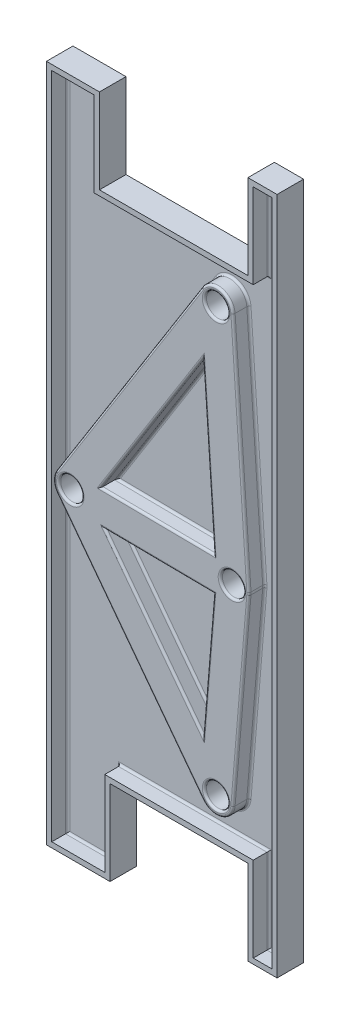
SolidWorks part; units mm, degrees
ref_plane "Plan de face" through (0, 0, 0) normal (0, 0, 1) x (1, 0, 0)
ref_plane "Plan de dessus" through (0, 0, 0) normal (0, 1, 0) x (1, 0, 0)
ref_plane "Plan de droite" through (0, 0, 0) normal (1, 0, 0) x (0, 0, -1)
sketch "Esquisse1" plane through (0, 0, 0) normal (0, 0, 1) x (1, 0, 0)
  line L0 (12, -64) -> (19.5, -64)
  line L1 (-12, -64) -> (12, -64)
  line L2 (-12, -64) -> (-12, 64)
  line L3 (-12, 64) -> (12, 64)
  line L4 (12, -64) -> (12, 64)
  line L5 (19.5, -64) -> (19.5, 64)
  line L6 (19.5, 64) -> (12, 64)
  line L7 (-19.5, -3.7001) -> (-24, -3.7001) construction
  line L8 (-12, -64) -> (-24, -64)
  line L9 (-12, -64) -> (-12, 64)
  line L10 (-12, -64) -> (-12, 64)
  line L11 (-12, 64) -> (-24, 64)
  line L12 (-24, -64) -> (-24, 64)
  line L13 (-24, -3.7001) -> (-19.5, -3.7001)
  line L15 (-14, 64) -> (14, 64)
  line L16 (-14, 64) -> (-14, 48)
  line L17 (14, -48) -> (14, -64)
  line L18 (-12, -48) -> (14, -48)
  line L19 (-12, -64) -> (-12, -48)
  line L20 (-14, 48) -> (14, 48)
  line L22 (14, 64) -> (14, 48)
  line L23 (-14, 48) -> (-14, 64)
  line L27 (14, 64) -> (14, 48)
  line L28 (14, 48) -> (-14, 48)
  circle A0 centre (-19.5, -3.7001) radius 1.9963
  circle A1 centre (-8, 56) radius 2.35 construction
  circle A2 centre (-8, -56) radius 2.35 construction
  circle A3 centre (8, 56) radius 2.35 construction
  circle A4 centre (-8, 56) radius 2.35
  circle A5 centre (-8, -56) radius 2.35
  circle A6 centre (8, 56) radius 2.35
  circle A7 centre (8, -56) radius 2.35 construction
  circle A8 centre (8, -56) radius 2.35
  circle A9 centre (11, -4.0114) radius 2
  dimension "D2" = 4
  dimension "D1" = 7.5
  dimension "D3" = 12
  dimension "D5" = 4.5
extrude "Boss.-Extru.2" add sketch "Esquisse1" along normal blind 5 contours L12 L8 L2 L11 | A9 L4 L3 L2 L1 A8 A6 A5 A4 | A9 L4 L0 L5 L6
sketch "Esquisse2" plane through (0, 0, 5) normal (0, 0, 1) x (1, 0, 0)
  line L24 (15, 63) -> (15, 47)
  line L25 (15, 47) -> (-15, 47)
  line L26 (-15, 47) -> (-15, 63)
  line L27 (-15, 63) -> (-23, 63)
  line L28 (-23, 63) -> (-23, -63)
  line L29 (-23, -63) -> (-13, -63)
  line L30 (-13, -63) -> (-13, -47)
  line L31 (-13, -47) -> (15, -47)
  line L32 (15, -47) -> (15, -63)
  line L33 (15, -63) -> (18.5, -63)
  line L34 (18.5, -63) -> (18.5, 63)
  line L35 (18.5, 63) -> (15, 63)
  line L36 (15, 63) -> (15, 47)
  line L37 (15, 47) -> (-15, 47)
  line L38 (-15, 47) -> (-15, 63)
  line L39 (-15, 63) -> (-23, 63)
  line L40 (-23, 63) -> (-23, -63)
  line L41 (-23, -63) -> (-13, -63)
  line L42 (-13, -63) -> (-13, -47)
  line L43 (-13, -47) -> (15, -47)
  line L44 (15, -47) -> (15, -63)
  line L45 (15, -63) -> (18.5, -63)
  line L46 (18.5, -63) -> (18.5, 63)
  line L47 (18.5, 63) -> (15, 63)
  dimension "D1" = 1
extrude "Enlèv. mat.-Extru.1" cut sketch "Esquisse2" against normal blind 3
sketch "Esquisse3" plane through (0, 0, 2) normal (0, 0, 1) x (1, 0, 0)
  circle A0 centre (8, -40) radius 2.2 construction
  circle A1 centre (8, -40) radius 2.2
  circle A2 centre (11, -4.0114) radius 2.2 construction
  circle A3 centre (11, -4.0114) radius 2.2
  circle A4 centre (-19.5, -3.7001) radius 2.2 construction
  circle A5 centre (-19.5, -3.7001) radius 2.2
  circle A6 centre (8, 40) radius 2.2 construction
  circle A7 centre (8, 40) radius 2.2
extrude "Enlèv. mat.-Extru.2" cut sketch "Esquisse3" against normal blind 3
sketch "Esquisse4" plane through (0, 0, 2) normal (0, 0, 1) x (1, 0, 0)
  circle A0 centre (8, -40) radius 2.2 construction
  circle A1 centre (8, -40) radius 2.2
  circle A2 centre (8, 40) radius 2.2 construction
  circle A3 centre (-19.5, -3.7001) radius 2.2 construction
  circle A4 centre (11, -4.0114) radius 2.2 construction
  circle A5 centre (8, 40) radius 2.2
  circle A6 centre (-19.5, -3.7001) radius 2.2
  circle A7 centre (11, -4.0114) radius 2.2
  circle A8 centre (-19.5, -3.7001) radius 3.2
  circle A9 centre (8, 40) radius 3.2
  circle A10 centre (11, -4.0114) radius 3.2
  circle A11 centre (8, -40) radius 3.2
  dimension "D1" = 1
extrude "Boss.-Extru.3" add sketch "Esquisse4" along normal blind 3
sketch "Esquisse5" plane through (0, 0, 2) normal (0, 0, 1) x (1, 0, 0)
  line L0 (5.4493, -41.9323) -> (-22.0507, -5.6325)
  line L2 (11.1889, -40.2658) -> (14.2091, -4.0356)
  line L3 (5.5052, -31.4076) -> (-13.0109, -6.9665)
  line L4 (5.4756, 29.9802) -> (-13.7423, -0.5587)
  line L5 (7.5721, -0.7762) -> (-13.7423, -0.5587)
  line L6 (11.1926, 40.2176) -> (14.2091, -4.0356)
  line L7 (7.5251, -7.1761) -> (-13.0109, -6.9665)
  line L8 (7.5721, -0.7762) -> (5.4756, 29.9802)
  line L9 (5.2916, 41.7043) -> (-22.2084, -1.9958)
  line L12 (5.5052, -31.4076) -> (7.5251, -7.1761)
  circle A0 centre (8, -40) radius 3.2 construction
  arc A1 (11.1889, -40.2658) -> (5.4493, -41.9323) centre (8, -40) ccw
  circle A2 centre (11, -4.0114) radius 3.2 construction
  circle A3 centre (11, -4.0114) radius 3.2
  circle A4 centre (-19.5, -3.7001) radius 3.2 construction
  circle A5 centre (-19.5, -3.7001) radius 3.2
  circle A6 centre (8, 40) radius 3.2 construction
  arc A7 (5.2916, 41.7043) -> (11.1926, 40.2176) centre (8, 40) ccw
  circle M16 centre (11, -4.0114) radius 3.2
  circle M17 centre (-19.5, -3.7001) radius 3.2
  circle M30 centre (8, 40) radius 3.2
  circle M31 centre (8, -40) radius 3.2
  dimension "D1" = 138.088
  dimension "D2" = 6.4
  dimension "D3" = 6.4
  dimension "D4" = 143.919
  dimension "D5" = 6.4
  dimension "D6" = 3.2
  dimension "D7" = 3.2
extrude "Boss.-Extru.4" add sketch "Esquisse5" along normal up to surface (3 mm away) contours L9 L0 L2 L6 L12 L3 L7 L8 L5 L4 M30 M17 M31 M16 up to face at (11.2, -40, 5)
fillet "Congé1" radius 0.4 18 edges at (-4.1334, 14.7108, 5) (-3.0851, -0.6675, 5) (6.5238, 14.602, 5) (10.2, -40, 5) (13.2, -4.0114, 5) (10.2, 40, 5) (-17.3, -3.7001, 5) (-8.4584, 19.8543, 5) (8.7818, 43.103, 5) (12.6926, 18.2119, 5) (14.1999, -4.0356, 5) (12.6889, -22.2715, 5) (8.8923, -43.0731, 5) (-22.697, -3.8387, 5) (6.5151, -19.2918, 5) (-2.7429, -7.0713, 5) (-3.7528, -19.187, 5) (-8.3007, -23.7824, 5)
fillet "Congé2" radius 0.4 20 edges at (18.5, 0, 2) (16.75, -63, 2) (15, -55, 2) (1, -47, 2) (-13, -55, 2) (-18, -63, 2) (-23, 0, 2) (-19, 63, 2) (-15, 55, 2) (0, 47, 2) (15, 55, 2) (16.75, 63, 2) (8.7818, 43.103, 2) (-8.4584, 19.8543, 2) (-22.697, -3.8387, 2) (-8.3007, -23.7824, 2) (8.8923, -43.0731, 2) (12.6889, -22.2715, 2) (14.1999, -4.0356, 2) (12.6926, 18.2119, 2)
fillet "Congé3" radius 0.4 6 edges at (6.5238, 14.602, 2) (-3.0851, -0.6675, 2) (-4.1334, 14.7108, 2) (6.5151, -19.2918, 2) (-3.7528, -19.187, 2) (-2.7429, -7.0713, 2)
